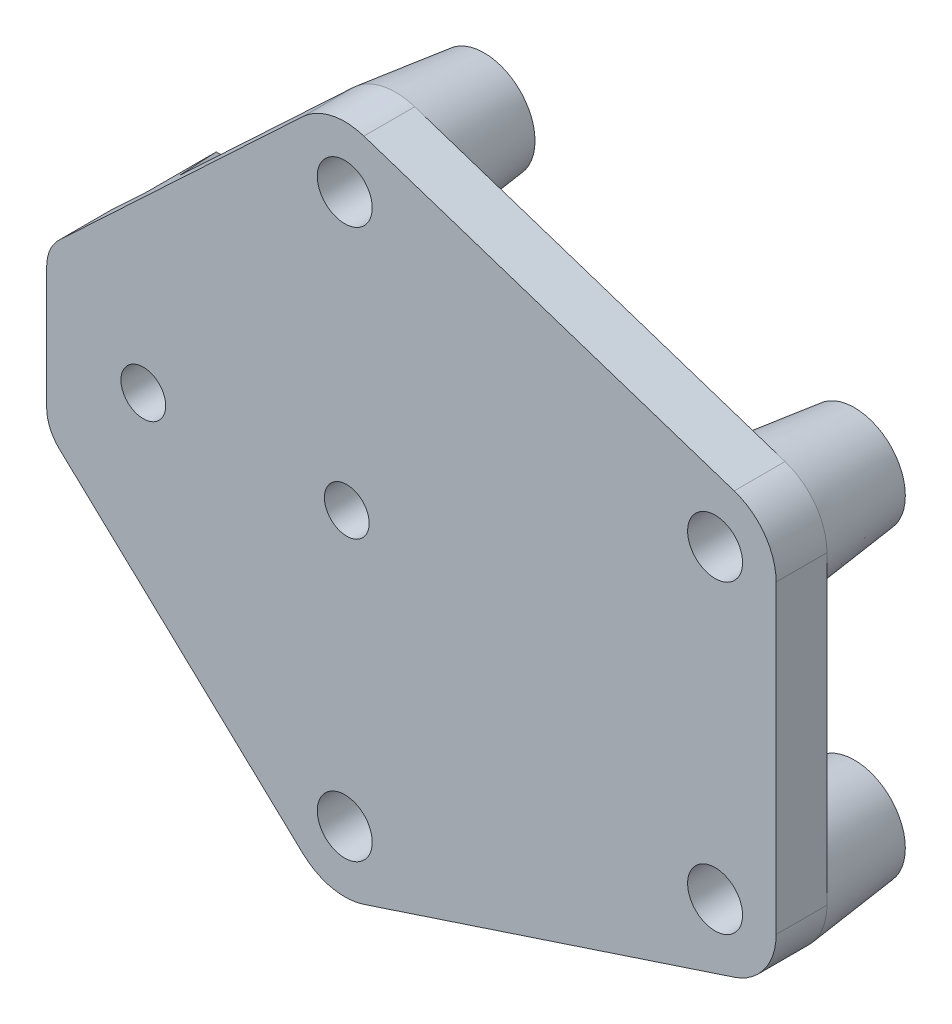
SolidWorks part; units mm, degrees
note: '?' marks a value the reader was unsure of. The reader was unsure of these and kept them because the rebuilt part matched: shared geometry of "草图4<3>", "草图1<4>".
ref_plane "前视基准面" through (0, 0, 0) normal (0, 0, 1) x (1, 0, 0)
ref_plane "上视基准面" through (0, 0, 0) normal (0, 1, 0) x (1, 0, 0)
ref_plane "右视基准面" through (0, 0, 0) normal (1, 0, 0) x (0, 0, -1)
sketch "草图1" plane through (0, 0, 0) normal (0, 0, 1) x (1, 0, 0)
  line L0 (-612.4365, 0) -> (30009.3904, 0) construction
  line L1 (-611.4109, 10) -> (30010.416, 10) construction
  line L2 (-607.9921, -10) -> (30013.8348, -10) construction
  line L3 (0, -612.4365) -> (0, 30009.3904) construction
  line L4 (-10, -612.4365) -> (-10, 30009.3904) construction
  line L5 (10, -614.6741) -> (10, 30007.1528) construction
  line L6 (-24.2, 27) -> (-24.2, -27) construction
  line L7 (-16.3214, 32.6983) -> (20.0786, 20.6983)
  line L8 (24.2, 15) -> (24.2, -15)
  line L9 (-32, -12.3) -> (-42.6321, -12.3)
  line L10 (-32, 12.3) -> (-42.6321, 12.3)
  line L11 (-32, 12.3) -> (-13, 12.3)
  line L12 (-32, 10.3) -> (-13, 10.3)
  line L13 (-13, 12.3) -> (-13, 10.3)
  line L14 (20.0786, -20.6983) -> (-16.3214, -32.6983)
  line L15 (-32, -10.3) -> (-13, -10.3)
  line L16 (-32, -12.3) -> (-13, -12.3)
  line L17 (-13, -12.3) -> (-13, -10.3)
  line L18 (-42.6321, 12.3) -> (-42.6321, 10.3)
  line L19 (-33.5, 10) -> (-33.5, -10) construction
  line L20 (-47.5, 6) -> (-47.5, -6)
  line L21 (-42.6321, 10.3) -> (-32, 10.3)
  line L22 (-42.6321, -12.3) -> (-42.6321, -10.3)
  line L23 (-22.3059, 31.3752) -> (-46.2372, 8.9168)
  line L24 (-22.3059, -31.3752) -> (-46.2372, -8.9168)
  line L25 (-42.6321, -10.3) -> (-32, -10.3)
  circle A0 centre (18.2, 27) radius 11.5 construction
  circle A1 centre (-18.2, 27) radius 11.5 construction
  circle A2 centre (-18.2, -27) radius 11.5 construction
  circle A3 centre (18.2, 15) radius 11.5 construction
  circle A4 centre (18.2, 15) radius 2.7
  circle A5 centre (-18.2, 27) radius 6
  circle A6 centre (-16, 14) radius 1.7 construction
  circle A7 centre (18.2, 15) radius 5 construction
  circle A8 centre (-18.2, 27) radius 2.7
  circle A9 centre (-18.2, -27) radius 2.7
  circle A10 centre (-18.2, 27) radius 5 construction
  circle A11 centre (-18.2, -27) radius 5 construction
  circle A12 centre (18.2, 15) radius 6
  circle A13 centre (18.2, -15) radius 5 construction
  circle A14 centre (-16, -14) radius 1.7 construction
  circle A15 centre (-18.2, -27) radius 6
  circle A16 centre (-18, 0) radius 2.2
  circle A17 centre (-38, 0) radius 2.2
  circle A18 centre (-31, 18) radius 2.2 construction
  circle A19 centre (-31, -18) radius 2.2 construction
  circle A20 centre (18.2, -15) radius 11.5 construction
  circle A21 centre (18.2, -15) radius 6
  circle A22 centre (18.2, -15) radius 2.7
  circle A23 centre (-18, 0) radius 4 construction
  arc A26 (-47.5, -6) -> (-43.525, -9.9999) centre (-43.5, -6) ccw
  arc A27 (-47.5, 6) -> (-43.2462, 9.9919) centre (-43.5, 6) cw
  point P48 (-31.5, 0)
  point P54 (-31.5, 0)
  point P82 (-47.5, -10)
  point P85 (-47.5, 10)
  dimension "D5" = 23
  dimension "D6" = 27
  dimension "D7" = 15
  dimension "D9" = 12
  dimension "D10" = 8
  dimension "D11" = 5.4
  dimension "D12" = 10
  dimension "D8" = 4.4
  dimension "D23" = 3.4
  dimension "D24" = 4.4
  dimension "D35" = 4
  dimension "D1" = 20
  dimension "D2" = 10
  dimension "D3" = 20
  dimension "D4" = 10
  dimension "D13" = 18.2
  dimension "D14" = 6
  dimension "D15" = 12
  dimension "D16" = 2
  dimension "D17" = 20.6
  dimension "D18" = 20
  dimension "D19" = 14.2
  dimension "D20" = 24.6
  dimension "D21" = 16
  dimension "D22" = 4
  dimension "D25" = 8
  dimension "D26" = 21
  dimension "D28" = 13
  dimension "D29" = 5
  dimension "D34" = 14
extrude "凸台-拉伸1" add sketch "草图1" along normal blind 5
ref_axis "基准轴1" through (-18.2, 27, 5) along (0, 0, -1)?
ref_axis "基准轴2" through (18.2, 15, 5) along (0, 0, -1)?
ref_plane "基准面2" through (6.2444, 18.9414, 0) normal (-0.3131, -0.9497, 0) x (-0.9497, 0.3131, 0)
sketch "草图4" plane through (6.2444, 18.9414, 0) normal (-0.3131, -0.9497, 0) x (-0.9497, 0.3131, 0)
  line L1 (-7.5885, 8.7) -> (-9.8885, 8.7)
  line L2 (25.7385, 0) -> (25.7385, 29798.822) construction
  line L3 (-6.5885, 0) -> (-7.5885, 8.7)
  line L4 (-9.8885, 0) -> (-6.5885, 0)
  line L5 (-9.8885, 8.7) -> (-9.8885, 0)
  line L10 (25.7385, -5) -> (25.7385, 0) construction
  line L11 (-12.5885, -4.4528) -> (-12.5885, 29794.3692) construction
  line L12 (-12.5885, -5) -> (-12.5885, 0) construction
  line L13 (25.7385, 0) -> (28.4385, 0) construction
  line L14 (31.0078, 0) -> (25.7385, 0) construction
  line L16 (28.4385, 0) -> (31.7385, 0)
  line L17 (31.7385, 0) -> (30.7385, 8.7)
  line L18 (30.7385, 8.7) -> (28.4385, 8.7)
  line L19 (28.4385, 8.7) -> (25.7385, 8.7) construction
  line L20 (28.4385, 8.7) -> (28.4385, 0)
  line L21 (25.7385, 8.7) -> (25.7385, 0) construction
  point P7 (0, 0)
  dimension "D2" = 2
  dimension "D3" = 5
  dimension "D7" = 2.7
  dimension "D8" = 6
  dimension "D9" = 8.7
  dimension "D10" = 5
revolve "旋转1" add sketch "草图4" angle 360 about L11
revolve "旋转2" add sketch "草图4<3>" angle 360 about L2
sketch "草图4<3>" plane through (6.2444, 18.9414, 0) normal (-0.3131, -0.9497, 0) x (-0.9497, 0.3131, 0) same geometry as "草图4"
mirror "镜向1" about plane through (0, 0, 0) normal (0, 1, 0) of "旋转2", "旋转1"
extrude "凸台-拉伸2" add sketch "草图1<4>" against normal blind 6.8
sketch "草图1<4>" plane through (0, 0, 0) normal (0, 0, 1) x (1, 0, 0) same geometry as "草图1"
chamfer "倒角1" distance 3 distance2 6.8 1 edges at (-27.8161, 12.3, 0)
chamfer "倒角2" distance 6.8 distance2 3 1 edges at (-27.8161, -12.3, 0)
sketch "草图5" [suppressed] plane through (0, 0, 0) normal (0, 0, -1) x (-1, 0, 0)
  line L0 (39.5, 5) -> (39.5, -5) construction
  line L1 (41, 5) -> (41, -5)
  line L2 (38, 5) -> (38, -5)
  arc A0 (41, 5) -> (38, 5) centre (39.5, 5) ccw
  arc A1 (38, -5) -> (41, -5) centre (39.5, -5) ccw
  circle A2 centre (39.5, -5) radius 1.5 construction
  point P4 (39.5, 0)
extrude "切除-拉伸1" [suppressed] cut sketch "草图5" against normal blind 2.5
